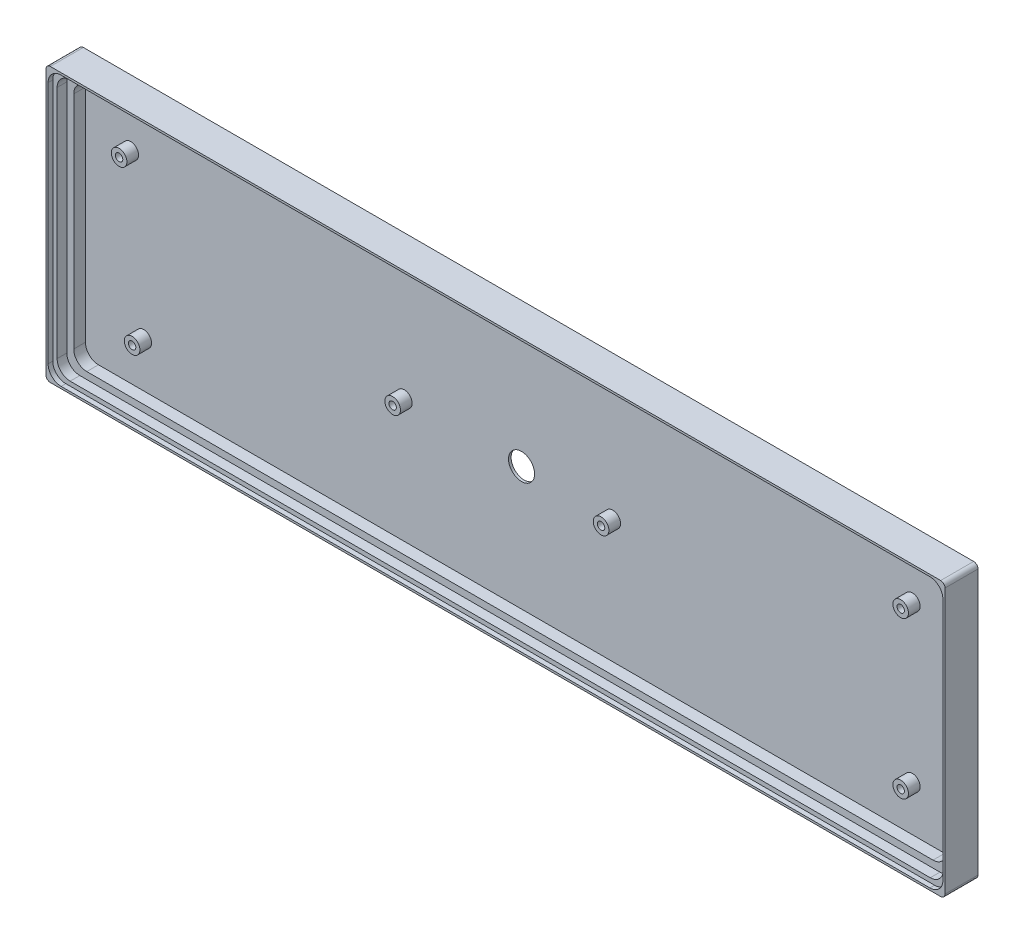
SolidWorks part; units mm, degrees
ref_plane "Front" through (0, 0, 0) normal (0, 0, 1) x (1, 0, 0)
ref_plane "Top" through (0, 0, 0) normal (0, 1, 0) x (1, 0, 0)
ref_plane "Right" through (0, 0, 0) normal (1, 0, 0) x (0, 0, -1)
sketch "Sketch1" plane through (0, 0, 0) normal (0, 0, 1) x (1, 0, 0)
  line L0 (164.338, 50.038) -> (-164.338, 50.038)
  line L1 (161.9885, -47.6885) -> (-161.9885, -47.6885)
  line L2 (161.9885, -47.6885) -> (161.9885, 47.6885)
  line L3 (161.9885, 47.6885) -> (-161.9885, 47.6885)
  line L4 (-161.9885, -47.6885) -> (-161.9885, 47.6885)
  line L5 (0, 47.6885) -> (0, -47.6885) construction
  line L6 (161.9885, 0) -> (-161.9885, 0) construction
  line L7 (163.576, -49.276) -> (-163.576, -49.276)
  line L8 (163.576, -49.276) -> (163.576, 49.276)
  line L9 (163.576, 49.276) -> (-163.576, 49.276)
  line L10 (-163.576, -49.276) -> (-163.576, 49.276)
  line L11 (0, 49.276) -> (0, -49.276) construction
  line L12 (163.576, 0) -> (-163.576, 0) construction
  line L13 (-164.338, -50.038) -> (-164.338, 50.038)
  line L14 (164.338, -50.038) -> (-164.338, -50.038)
  line L15 (164.338, -50.038) -> (164.338, 50.038)
  line L16 (159.4485, 45.1485) -> (-159.4485, 45.1485)
  line L17 (-159.4485, -45.1485) -> (-159.4485, 45.1485)
  line L18 (159.4485, -45.1485) -> (-159.4485, -45.1485)
  line L19 (159.4485, -45.1485) -> (159.4485, 45.1485)
  point P0 (0, 0)
  point P4 (0, 0)
  dimension "D1" = 95.377
  dimension "D2" = 323.977
  dimension "D3" = 1.5875
  dimension "D4" = 1.5875
  dimension "D5" = 0.762
  dimension "D6" = 2.54
extrude "Boss-Extrude1" add sketch "Sketch1" along normal blind 2.54 contours L4 L1 L2 L3 | L10 L7 L8 L9 L1 L4 L3 L2 | L14 L15 L0 L13 L7 L10 L9 L8 | L18 L19 L16 L17 region at (163.9944, 0, 0) region at (0, -47.3508, 0) region at (0, -48.9343, 0) region at (0, 0, 0)
extrude "Boss-Extrude2" add sketch "Sketch1<3>" along normal blind 12.065 contours L14 L15 L0 L13 L7 L10 L9 L8 region at (163.9944, 0, 0)
sketch "Sketch1<3>" plane through (0, 0, 0) normal (0, 0, 1) x (1, 0, 0) same geometry as "Sketch1"
extrude "Boss-Extrude3" add sketch "Sketch1<4>" along normal offset from surface (10.3505 mm away) 1.7145 contours L10 L7 L8 L9 L1 L4 L3 L2 region at (0, -48.9343, 0) up to face at (0, 0, 12.065)
sketch "Sketch1<4>" plane through (0, 0, 0) normal (0, 0, 1) x (1, 0, 0) same geometry as "Sketch1"
extrude "Boss-Extrude4" add sketch "Sketch1<5>" along normal offset from surface (6.8072 mm away) 3.5433 contours L4 L1 L2 L3 L19 L18 L17 L16 region at (0, -47.3508, 0) up to face at (0, 0, 10.3505)
sketch "Sketch1<5>" plane through (0, 0, 0) normal (0, 0, 1) x (1, 0, 0) same geometry as "Sketch1"
sketch "Sketch2" plane through (0, 0, 2.54) normal (0, 0, 1) x (1, 0, 0)
  circle A0 centre (-142.875, 28.575) radius 1.3526
  circle A1 centre (-138.1125, -28.575) radius 1.3526
  circle A2 centre (-42.8625, 0) radius 1.3526
  circle A3 centre (33.3375, 0) radius 1.3526
  circle A4 centre (142.875, -28.575) radius 2.8575
  circle A5 centre (33.3375, 0) radius 2.8575
  circle A6 centre (142.875, 28.575) radius 2.8575
  circle A7 centre (-42.8625, 0) radius 2.8575
  circle A12 centre (142.875, -28.575) radius 1.3526
  circle A13 centre (142.875, 28.575) radius 1.3526
  circle A14 centre (-138.1125, -28.575) radius 2.8575
  circle A15 centre (-142.875, 28.575) radius 2.8575
  dimension "D2" = 2.7051
  dimension "D1" = 5.715
extrude "Boss-Extrude5" add sketch "Sketch2" along normal up to surface (4.2672 mm away) contours A4 A12 | A6 A13 | A7 A2 | A5 A3 | A15 A0 | A14 A1 region at (140.0983, -28.575, 2.54) region at (30.5608, 0, 2.54) region at (140.0983, 28.575, 2.54) region at (-45.6392, 0, 2.54) region at (-140.8892, -28.575, 2.54) region at (-145.6517, 28.575, 2.54) up to face at (0, 0, 6.8072)
fillet "Fillet1" radius 4.7625 12 edges at (-163.576, -49.276, 11.2077) (-161.9885, -47.6885, 8.5788) (161.9885, -47.6885, 8.5788) (163.576, -49.276, 11.2077) (161.9885, 47.6885, 8.5788) (163.576, 49.276, 11.2077) (-161.9885, 47.6885, 8.5788) (-163.576, 49.276, 11.2077) (-159.4485, -45.1485, 4.6736) (159.4485, -45.1485, 4.6736) (159.4485, 45.1485, 4.6736) (-159.4485, 45.1485, 4.6736)
fillet "Fillet2" radius 1.5875 4 edges at (164.338, -50.038, 6.0325) (-164.338, -50.038, 6.0325) (-164.338, 50.038, 6.0325) (164.338, 50.038, 6.0325)
sketch "Sketch3" plane through (0, 0, 0) normal (0, 0, -1) x (-1, 0, 0)
  line L1 (-26.9875, -15.875) -> (26.9875, -15.875)
  line L2 (-30.1625, -12.7) -> (-30.1625, 12.7)
  line L3 (-26.9875, 15.875) -> (26.9875, 15.875)
  line L4 (30.1625, -12.7) -> (30.1625, 12.7)
  line L5 (0, 15.875) -> (0, -15.875) construction
  line L6 (-30.1625, 0) -> (30.1625, 0) construction
  arc A0 (-26.9875, -15.875) -> (-30.1625, -12.7) centre (-26.9875, -12.7) cw
  arc A1 (-26.9875, 15.875) -> (-30.1625, 12.7) centre (-26.9875, 12.7) ccw
  arc A2 (26.9875, 15.875) -> (30.1625, 12.7) centre (26.9875, 12.7) cw
  arc A3 (26.9875, -15.875) -> (30.1625, -12.7) centre (26.9875, -12.7) ccw
  point P0 (0, 0)
  point P6 (-30.1625, -15.875)
  point P11 (30.1625, 15.875)
  point P14 (30.1625, -15.875)
  dimension "D3" = 3.175
  dimension "D1" = 60.325
  dimension "D2" = 31.75
extrude "Cut-Extrude1" cut sketch "Sketch3" against normal blind 1.5875
sketch "Sketch4" plane through (0, 0, 2.54) normal (0, 0, 1) x (1, 0, 0)
  circle A0 centre (0, 0) radius 4.7625
  dimension "D1" = 9.525
extrude "Cut-Extrude2" cut sketch "Sketch4" against normal through all
